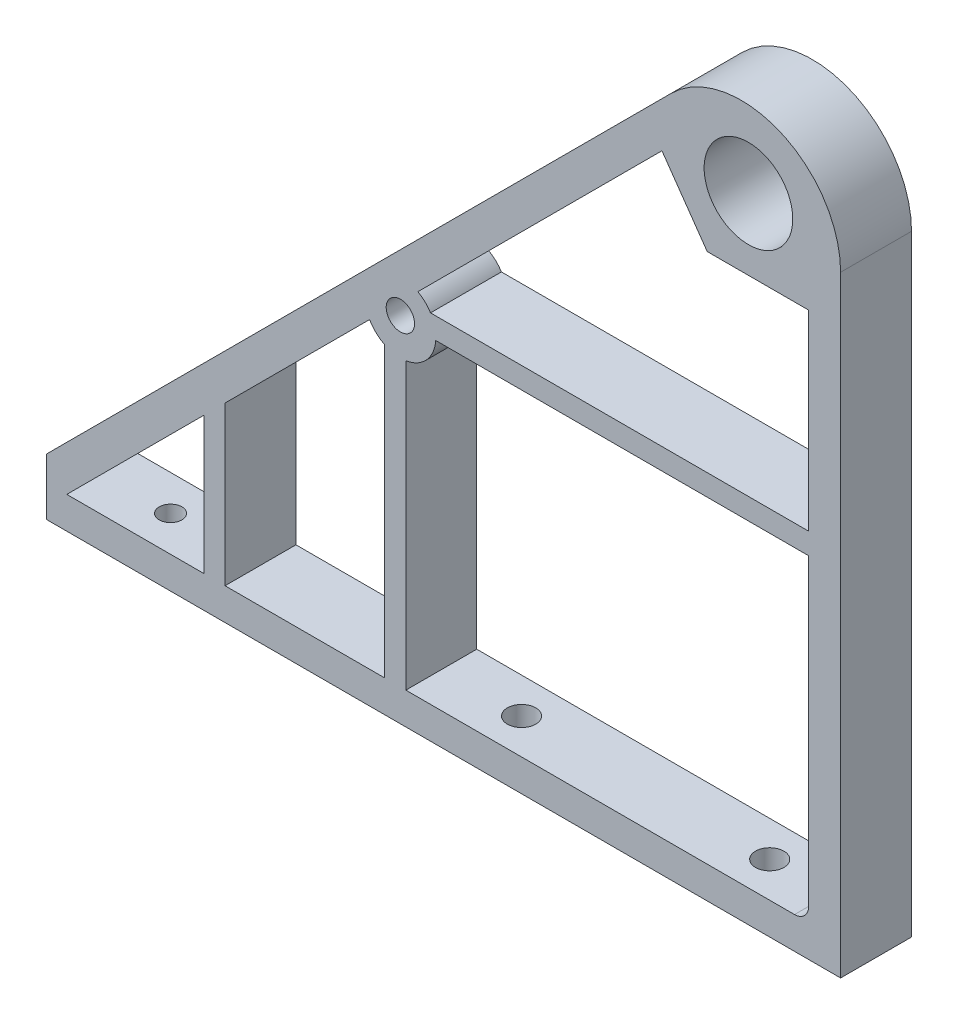
SolidWorks part; units mm, degrees
material "Magnesium Alloy"
ref_plane "Front Plane" through (0, 0, 0) normal (0, 0, 1) x (1, 0, 0)
ref_plane "Top Plane" through (0, 0, 0) normal (0, 1, 0) x (1, 0, 0)
ref_plane "Right Plane" through (0, 0, 0) normal (1, 0, 0) x (0, 0, -1)
sketch "Sketch1" plane through (0, 0, 0) normal (0, 0, 1) x (1, 0, 0)
  line L0 (-152.4, 0) -> (0, 0)
  line L1 (55, 0) -> (-55, 0) construction
  line L2 (0, 0) -> (0, 152.4)
  line L3 (0, -55) -> (0, 55) construction
  line L4 (0, 152.4) -> (-152.4, 0)
  dimension "D1" = 152.4
  dimension "D2" = 152.4
extrude "Boss-Extrude1" add sketch "Sketch1" along normal blind 12.7
fillet "Fillet1" radius 17.78 1 edges at (0, 152.4, 6.35)
sketch "Sketch2" plane through (0, 0, 12.7) normal (0, 0, 1) x (1, 0, 0)
  line L0 (0, -6.985) -> (0, 6.985) construction
  line L1 (-30.3524, 122.0476) -> (-152.4, 0) construction
  line L2 (-142.24, 0) -> (-152.4, 0)
  line L3 (6.985, 0) -> (-6.985, 0) construction
  line L4 (-152.4, 0) -> (-142.24, 10.16)
  line L5 (-142.24, 10.16) -> (-142.24, 0)
  circle A0 centre (-16.51, 113.4394) radius 7.9375
  dimension "D1" = 16.51
  dimension "D2" = 15.875
  dimension "D3" = 10.16
extrude "Cut-Extrude1" cut sketch "Sketch2" against normal blind 25.4
sketch "Sketch4" plane through (0, 0, 0) normal (0, 0, 1) x (1, 0, 0)
  line L0 (-138.6028, 5.715) -> (-114.0683, 5.715)
  line L1 (-114.0683, 5.715) -> (-114.0683, 30.2494)
  line L2 (-114.0683, 30.2494) -> (-138.6028, 5.715)
  line L3 (-110.2583, 5.715) -> (-110.2583, 34.0594)
  line L5 (-81.6833, 5.715) -> (-110.2583, 5.715)
  line L6 (-30.3524, 122.0476) -> (-142.24, 10.16) construction
  line L7 (6.985, 0) -> (-6.985, 0) construction
  line L9 (-81.6833, 5.715) -> (-81.6833, 62.6344)
  line L10 (-81.6833, 62.6344) -> (-110.2583, 34.0594)
  line L12 (-77.8733, 66.4444) -> (-5.715, 66.4444)
  line L13 (-23.893, 100.7344) -> (-32.0022, 112.3156)
  line L14 (-32.0022, 112.3156) -> (-77.8733, 66.4444)
  line L16 (-77.8733, 5.715) -> (-5.715, 5.715)
  line L17 (-23.893, 100.7344) -> (-5.715, 100.7344)
  line L19 (-5.715, 66.4444) -> (-5.715, 100.7344)
  line L22 (-77.8733, 62.6344) -> (-77.8733, 5.715)
  line L32 (-117.1937, 76.2) -> (-52.9571, 76.2) construction
  line L34 (-77.8733, 62.6344) -> (-5.715, 62.6344)
  line L35 (-5.715, 62.6344) -> (-5.715, 5.715)
  line L37 (0, -6.985) -> (0, 6.985) construction
  circle A1 centre (-16.51, 113.4394) radius 7.9375 construction
  dimension "D1" = 5.715
  dimension "D2" = 5.715
  dimension "D3" = 3.81
  dimension "D4" = 5.715
  dimension "D5" = 5.715
  dimension "D6" = 13.335
  dimension "D7" = 5.715
  dimension "D8" = 76.2
  dimension "D9" = 34.29
  dimension "D10" = 3.81
  dimension "D11" = 5.715
  dimension "D12" = 3.81
  dimension "D13" = 28.575
  dimension "D14" = 125
extrude "Cut-Extrude2" cut sketch "Sketch4" along normal blind 24.638
sketch "Sketch5" plane through (0, 5.715, 0) normal (0, 1, 0) x (1, 0, 0)
  line L0 (-142.24, -12.7) -> (0, -12.7) construction
  line L1 (-142.24, 0) -> (-142.24, -12.7) construction
  circle A0 centre (-126.365, -6.35) radius 2.032
  dimension "D3" = 4.064
  dimension "D1" = 6.35
  dimension "D2" = 15.875
extrude "Cut-Extrude3" cut sketch "Sketch5" against normal blind 12.7
sketch "Sketch6" plane through (0, 5.715, 0) normal (0, 1, 0) x (1, 0, 0)
  circle A0 centre (-126.365, -6.35) radius 4.1275
  dimension "D1" = 8.255
extrude "Cut-Extrude4" cut sketch "Sketch6" along normal blind 32.258
ref_axis "Axis1" through (-79.1433, 394.7208, 45.72) along (0, -1, 0)
ref_axis "Axis2" through (-79.1433, 394.7208, 45.72) along (0, -1, 0)
ref_axis "Axis3" through (-126.365, 0, 6.35) along (0, 1, 0)
ref_axis "Axis4" through (-126.8624, 389.3594, 272.2143) along (0, 1, 0)
ref_axis "Axis5" through (-126.365, 0, 6.35) along (0, 1, 0)
ref_axis "Axis6" through (-79.1433, 394.7208, 45.72) along (0, -1, 0)
ref_axis "Axis7" through (-126.365, 0, 6.35) along (0, 1, 0)
sketch "Sketch7" plane through (0, 5.715, 0) normal (0, 1, 0) x (1, 0, 0)
  line L0 (0, -6.985) -> (0, 6.985) construction
  line L1 (-69.9904, 0) -> (69.9904, 0) construction
  circle A0 centre (-19.05, -6.35) radius 2.54
  circle A1 centre (-63.5, -6.35) radius 2.54
  dimension "D1" = 5.08
  dimension "D4" = 5.08
  dimension "D2" = 19.05
  dimension "D3" = 6.35
  dimension "D5" = 44.45
extrude "Cut-Extrude5" cut sketch "Sketch7" against normal blind 12.7
fillet "Fillet2" radius 2.54 1 edges at (-5.715, 5.715, 6.35)
sketch "Sketch8" plane through (0, 0, 12.7) normal (0, 0, 1) x (1, 0, 0)
  circle A0 centre (-78.848, 63.0886) radius 6.35
  dimension "D1" = 12.7
extrude "Boss-Extrude2" add sketch "Sketch8" against normal blind 12.7
sketch "Sketch9" plane through (0, 0, 12.7) normal (0, 0, 1) x (1, 0, 0)
  circle A0 centre (-78.8533, 63.3313) radius 2.54
  dimension "D1" = 5.08
extrude "Cut-Extrude6" cut sketch "Sketch9" against normal blind 12.7
